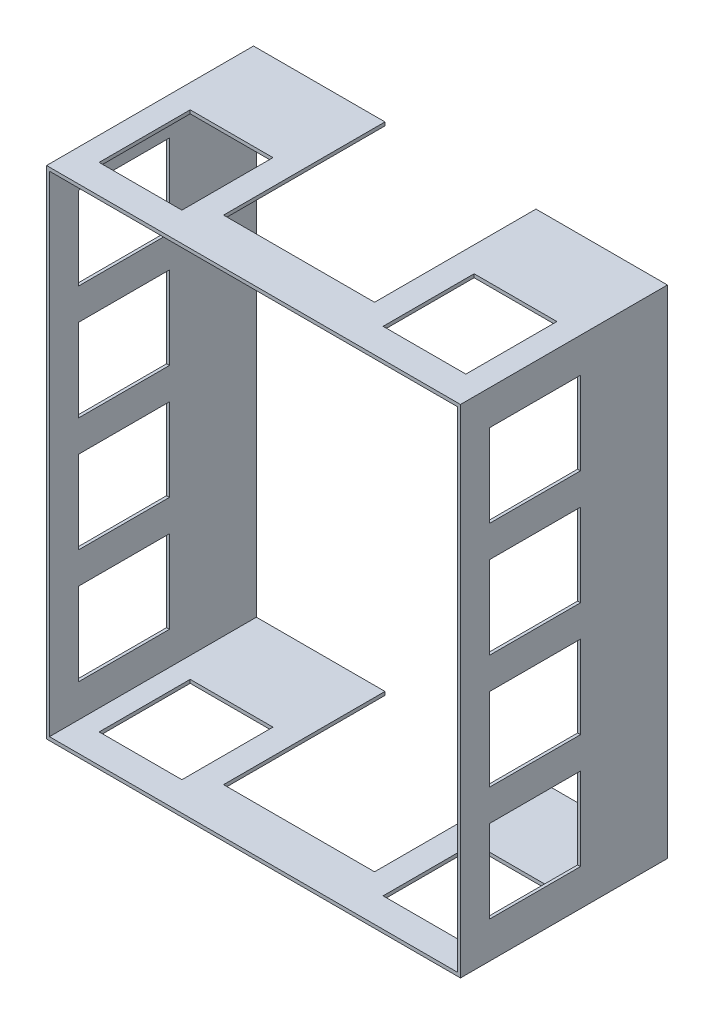
SolidWorks part; units mm, degrees
ref_plane "Plano frontal" through (0, 0, 0) normal (0, 0, 1) x (1, 0, 0)
ref_plane "Plano superior" through (0, 0, 0) normal (0, 1, 0) x (1, 0, 0)
ref_plane "Plano direito" through (0, 0, 0) normal (1, 0, 0) x (0, 0, -1)
sketch "Sketch1" plane through (0, 0, 38871.7002) normal (0, 0, 1) x (1, 0, 0)
  line L5 (-29782.6091, -4656.273) -> (-24782.6091, -4656.273)
  line L6 (-29782.6091, -4656.273) -> (-29782.6091, 1343.727)
  line L7 (-29782.6091, 1343.727) -> (-24782.6091, 1343.727)
  line L8 (-24782.6091, -4656.273) -> (-24782.6091, 1343.727)
  line L9 (-29782.6091, -4656.273) -> (-24782.6091, 1343.727) construction
  line L10 (-29782.6091, 1343.727) -> (-24782.6091, -4656.273) construction
  line L11 (-29747.6091, -4614.273) -> (-24817.6091, -4614.273)
  line L12 (-29747.6091, -4614.273) -> (-29747.6091, 1301.727)
  line L13 (-29747.6091, 1301.727) -> (-24817.6091, 1301.727)
  line L14 (-24817.6091, -4614.273) -> (-24817.6091, 1301.727)
  line L15 (-29747.6091, -4614.273) -> (-24817.6091, 1301.727) construction
  line L16 (-29747.6091, 1301.727) -> (-24817.6091, -4614.273) construction
  point P0 (-27282.6091, -1656.273)
  point P4 (-27282.6091, -1656.273)
  dimension "D1" = 5000
  dimension "D2" = 6000
  dimension "D3" = 35
extrude "Boss-Extrude1" add sketch "Sketch1" along normal blind 2500
sketch "Sketch2" plane through (-29782.6091, 0, 0) normal (-1, 0, 0) x (0, 0, 1)
  line L0 (38871.7002, 1343.727) -> (38871.7002, -4656.273) construction
  line L1 (41021.7002, -75.4632) -> (39921.7002, -75.4632)
  line L2 (41021.7002, -75.4632) -> (41021.7002, 924.5368)
  line L3 (41021.7002, 924.5368) -> (39921.7002, 924.5368)
  line L4 (39921.7002, -75.4632) -> (39921.7002, 924.5368)
  line L5 (41021.7002, -75.4632) -> (39921.7002, 924.5368) construction
  line L6 (41021.7002, 924.5368) -> (39921.7002, -75.4632) construction
  point P0 (40471.7002, 424.5368)
  dimension "D1" = 1050
  dimension "D2" = 1100
  dimension "D3" = 1000
extrude "Cut-Extrude1" cut sketch "Sketch2" against normal blind 5531
sketch "Sketch3" plane through (0, 1301.727, 0) normal (0, -1, 0) x (1, 0, 0)
  line L1 (-26067.6091, 41021.7002) -> (-25067.6091, 41021.7002)
  line L2 (-26067.6091, 41021.7002) -> (-26067.6091, 39921.7002)
  line L3 (-26067.6091, 39921.7002) -> (-25067.6091, 39921.7002)
  line L4 (-25067.6091, 41021.7002) -> (-25067.6091, 39921.7002)
  line L5 (-26067.6091, 41021.7002) -> (-25067.6091, 39921.7002) construction
  line L6 (-26067.6091, 39921.7002) -> (-25067.6091, 41021.7002) construction
  line L7 (-24817.6091, 38871.7002) -> (-29747.6091, 38871.7002) construction
  point P0 (-25567.6091, 40471.7002)
  dimension "D1" = 1050
  dimension "D2" = 1100
  dimension "D3" = 1000
  dimension "D4" = 250
extrude "Cut-Extrude2" cut sketch "Sketch3" along normal blind 7050 and the other way blind 2597
sketch "Sketch4" plane through (0, 868.9912, 38871.7002) normal (0, 0, 1) x (1, 0, 0)
  line L1 (-25853.0854, -311.4577) -> (-25053.0854, -311.4577)
  line L2 (-25853.0854, -311.4577) -> (-25853.0854, -1811.4577)
  line L3 (-25853.0854, -1811.4577) -> (-25053.0854, -1811.4577)
  line L4 (-25053.0854, -311.4577) -> (-25053.0854, -1811.4577)
  line L5 (-25853.0854, -311.4577) -> (-25053.0854, -1811.4577) construction
  line L6 (-25853.0854, -1811.4577) -> (-25053.0854, -311.4577) construction
  line L7 (-25853.0854, -1811.4577) -> (-25803.0854, -1811.4577)
  line L8 (-25853.0854, -1811.4577) -> (-25853.0854, -1761.4577)
  line L9 (-25853.0854, -1761.4577) -> (-25803.0854, -1761.4577)
  line L10 (-25803.0854, -1811.4577) -> (-25803.0854, -1761.4577)
  line L11 (-25053.0854, -1811.4577) -> (-25103.0854, -1811.4577)
  line L12 (-25053.0854, -1811.4577) -> (-25053.0854, -1761.4577)
  line L13 (-25053.0854, -1761.4577) -> (-25103.0854, -1761.4577)
  line L14 (-25103.0854, -1811.4577) -> (-25103.0854, -1761.4577)
  line L15 (-25053.0854, -311.4577) -> (-25103.0854, -311.4577)
  line L16 (-25053.0854, -311.4577) -> (-25053.0854, -361.4577)
  line L17 (-25053.0854, -361.4577) -> (-25103.0854, -361.4577)
  line L18 (-25103.0854, -311.4577) -> (-25103.0854, -361.4577)
  line L19 (-25853.0854, -311.4577) -> (-25803.0854, -311.4577)
  line L20 (-25853.0854, -311.4577) -> (-25853.0854, -361.4577)
  line L21 (-25853.0854, -361.4577) -> (-25803.0854, -361.4577)
  line L22 (-25803.0854, -311.4577) -> (-25803.0854, -361.4577)
  line L23 (-25853.0854, -1811.4577) -> (-25803.0854, -1811.4577)
  line L24 (-25853.0854, -1811.4577) -> (-25853.0854, -1761.4577)
  line L25 (-25853.0854, -1761.4577) -> (-25803.0854, -1761.4577)
  line L26 (-25803.0854, -1811.4577) -> (-25803.0854, -1761.4577)
  line L27 (-25053.0854, -1811.4577) -> (-25103.0854, -1811.4577)
  line L28 (-25053.0854, -1811.4577) -> (-25053.0854, -1761.4577)
  line L29 (-25053.0854, -1761.4577) -> (-25103.0854, -1761.4577)
  line L30 (-25103.0854, -1811.4577) -> (-25103.0854, -1761.4577)
  line L31 (-25053.0854, -311.4577) -> (-25103.0854, -311.4577)
  line L32 (-25053.0854, -311.4577) -> (-25053.0854, -361.4577)
  line L33 (-25053.0854, -361.4577) -> (-25103.0854, -361.4577)
  line L34 (-25103.0854, -311.4577) -> (-25103.0854, -361.4577)
  line L35 (-25853.0854, -311.4577) -> (-25803.0854, -311.4577)
  line L36 (-25853.0854, -311.4577) -> (-25853.0854, -361.4577)
  line L37 (-25853.0854, -361.4577) -> (-25803.0854, -361.4577)
  line L38 (-25803.0854, -311.4577) -> (-25803.0854, -361.4577)
  point P0 (-25453.0854, -1061.4577)
  dimension "D1" = 1500
  dimension "D2" = 800
  dimension "D3" = 50
extrude "Boss-Extrude3" [suppressed] add sketch "Sketch4" along normal blind 25 from offset 753 separate body contours L1 L22 L21 L2 L9 L10 L3 L14 L13 L4 L17 L18 | L3 L10 L9 L2 | L14 L3 L4 L13 | L1 L18 L17 L4 | L22 L1 L2 L21
sketch "Sketch5" [suppressed] plane through (0, 0, 38871.7002) normal (0, 0, 1) x (1, 0, 0)
  line L1 (-25053.0854, -942.4665) -> (-25103.0854, -942.4665)
  line L2 (-25053.0854, -942.4665) -> (-25053.0854, -892.4665)
  line L3 (-25053.0854, -892.4665) -> (-25103.0854, -892.4665)
  line L4 (-25103.0854, -942.4665) -> (-25103.0854, -892.4665)
  line L5 (-25853.0854, -942.4665) -> (-25803.0854, -942.4665)
  line L6 (-25853.0854, -942.4665) -> (-25853.0854, -892.4665)
  line L7 (-25853.0854, -892.4665) -> (-25803.0854, -892.4665)
  line L8 (-25803.0854, -942.4665) -> (-25803.0854, -892.4665)
  line L9 (-25853.0854, 557.5335) -> (-25803.0854, 557.5335)
  line L10 (-25853.0854, 557.5335) -> (-25853.0854, 507.5335)
  line L11 (-25853.0854, 507.5335) -> (-25803.0854, 507.5335)
  line L12 (-25803.0854, 557.5335) -> (-25803.0854, 507.5335)
  line L13 (-25053.0854, 557.5335) -> (-25103.0854, 557.5335)
  line L14 (-25053.0854, 557.5335) -> (-25053.0854, 507.5335)
  line L15 (-25053.0854, 507.5335) -> (-25103.0854, 507.5335)
  line L16 (-25103.0854, 557.5335) -> (-25103.0854, 507.5335)
  dimension "D1" = 50
extrude "Boss-Extrude4" [suppressed] add sketch "Sketch5" along normal up to next
pattern_linear "LPattern1" [suppressed] count 2 spacing 3660 count 2 spacing 2900 of bodies 105 106
sketch "Sketch6" plane through (0, -4656.273, 0) normal (0, -1, 0) x (1, 0, 0)
  line L1 (-28194.6091, 40821.7002) -> (-26370.6091, 40821.7002)
  line L2 (-28194.6091, 40821.7002) -> (-28194.6091, 38871.7002)
  line L3 (-28194.6091, 38871.7002) -> (-26370.6091, 38871.7002)
  line L4 (-26370.6091, 40821.7002) -> (-26370.6091, 38871.7002)
  line L5 (-29782.6091, 38871.7002) -> (-24782.6091, 38871.7002) construction
  line L6 (-29782.6091, 40121.7002) -> (-28194.6091, 40121.7002) construction
  line L7 (-29782.6091, 41371.7002) -> (-29782.6091, 38871.7002) construction
  line L8 (-24782.6091, 40121.7002) -> (-26370.6091, 40121.7002) construction
  line L9 (-24782.6091, 41371.7002) -> (-24782.6091, 38871.7002) construction
  dimension "D1" = 1824
  dimension "D2" = 1950
extrude "Cut-Extrude3" cut sketch "Sketch6" against normal blind 8265
pattern_linear "LPattern2" count 2 spacing 3430 along (-1, 0, 0) of "Cut-Extrude2"
pattern_linear "LPattern3" count 4 spacing 1380 along (0, -1, 0) of "Cut-Extrude1"
sketch "Sketch7" plane through (0, 0, 38871.7002) normal (0, 0, 1) x (1, 0, 0)
  line L0 (-22875.1811, 4188.5921) -> (-22875.1811, 2186.5306) construction
  line L1 (-24782.6091, 1343.727) -> (-24782.6091, 855.6477) construction
  circle A0 centre (-22875.1811, 3171.1862) radius 3000
  point P2 (-24991.764, 1497.629)
  point P8 (-24782.6091, 855.6477)
  dimension "D1" = 6000
  dimension "D2" = 488.0793
